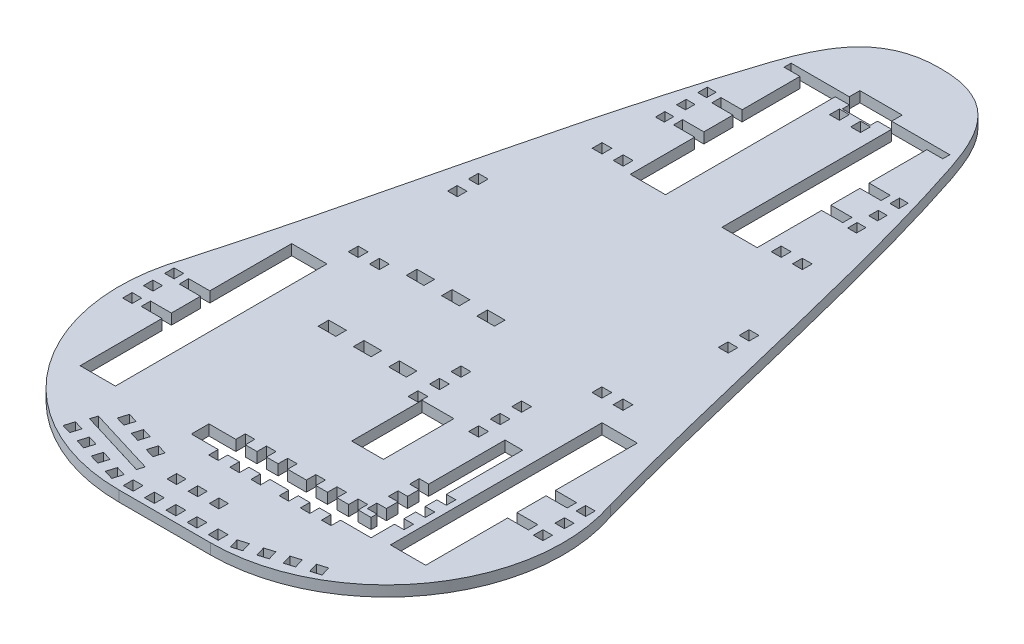
SolidWorks part; units mm, degrees
ref_plane "Front Plane" through (0, 0, 0) normal (0, 0, 1) x (1, 0, 0)
ref_plane "Top Plane" through (0, 0, 0) normal (0, 1, 0) x (1, 0, 0)
ref_plane "Right Plane" through (0, 0, 0) normal (1, 0, 0) x (0, 0, -1)
sketch "Sketch1" plane through (0, 0, 0) normal (0, 1, 0) x (1, 0, 0)
  line L0 (54.872, 210.7624) -> (54.872, -9.2376) construction
  line L1 (41.9035, -9.2376) -> (67.8405, -9.2376)
  line L6 (5.872, 75.7624) -> (15.872, 75.7624)
  line L7 (54.872, -9.2376) -> (64.872, -9.2376)
  line L8 (54.872, -9.2376) -> (44.872, -9.2376)
  line L9 (5.872, 75.7624) -> (5.872, 15.7624)
  line L10 (5.872, 15.7624) -> (15.872, 15.7624)
  line L11 (15.872, 75.7624) -> (15.872, 15.7624)
  line L12 (5.872, 75.7624) -> (15.872, 15.7624) construction
  line L13 (5.872, 15.7624) -> (15.872, 75.7624) construction
  line L18 (-0.128, 52.5374) -> (5.872, 52.5374)
  line L19 (-0.128, 52.5374) -> (-0.128, 49.8874)
  line L35 (103.872, 15.7624) -> (93.872, 15.7624)
  line L36 (93.872, 75.7624) -> (93.872, 15.7624)
  line L37 (103.872, 75.7624) -> (93.872, 75.7624)
  line L38 (103.872, 75.7624) -> (103.872, 15.7624)
  line L40 (36.872, 190.7624) -> (46.872, 190.7624)
  line L41 (36.872, 190.7624) -> (36.872, 140.7624)
  line L42 (36.872, 140.7624) -> (46.872, 140.7624)
  line L43 (46.872, 190.7624) -> (46.872, 140.7624)
  line L44 (36.872, 190.7624) -> (46.872, 140.7624) construction
  line L45 (36.872, 140.7624) -> (46.872, 190.7624) construction
  line L46 (10.872, 45.7624) -> (-10.2667, 45.7624) construction
  line L63 (72.872, 140.7624) -> (62.872, 140.7624)
  line L64 (62.872, 190.7624) -> (62.872, 140.7624)
  line L65 (72.872, 190.7624) -> (62.872, 190.7624)
  line L66 (72.872, 190.7624) -> (72.872, 140.7624)
  line L78 (114.572, 47.1124) -> (111.872, 44.4124) construction
  line L79 (114.572, 44.4124) -> (111.872, 47.1124) construction
  line L80 (114.572, 50.4124) -> (111.872, 53.1124) construction
  line L81 (114.572, 53.1124) -> (111.872, 50.4124) construction
  line L82 (109.7728, 38.9874) -> (103.7728, 41.6374) construction
  line L83 (109.7728, 41.6374) -> (103.7728, 38.9874) construction
  line L84 (109.872, 49.8874) -> (103.872, 52.5374) construction
  line L85 (109.872, 52.5374) -> (103.872, 49.8874) construction
  line L86 (111.7728, 41.1124) -> (111.7728, 38.4124)
  line L87 (114.4728, 38.4124) -> (111.7728, 38.4124)
  line L88 (114.4728, 41.1124) -> (114.4728, 38.4124)
  line L89 (111.872, 44.4124) -> (111.872, 47.1124)
  line L90 (114.572, 47.1124) -> (111.872, 47.1124)
  line L91 (114.572, 44.4124) -> (114.572, 47.1124)
  line L92 (41.872, 165.7624) -> (24.9145, 165.7624) construction
  line L93 (30.872, 172.4874) -> (36.872, 172.4874)
  line L94 (30.872, 172.4874) -> (30.872, 169.8874)
  line L95 (30.872, 169.8874) -> (36.872, 169.8874)
  line L96 (36.872, 172.4874) -> (36.872, 169.8874)
  line L97 (30.872, 172.4874) -> (36.872, 169.8874) construction
  line L98 (30.872, 169.8874) -> (36.872, 172.4874) construction
  line L103 (26.372, 161.1124) -> (28.872, 161.1124)
  line L104 (26.372, 173.1124) -> (28.872, 173.1124)
  line L105 (30.872, 161.6374) -> (36.872, 161.6374)
  line L106 (30.872, 161.6374) -> (30.872, 159.0374)
  line L107 (30.872, 159.0374) -> (36.872, 159.0374)
  line L108 (36.872, 161.6374) -> (36.872, 159.0374)
  line L109 (30.872, 161.6374) -> (36.872, 159.0374) construction
  line L110 (30.872, 159.0374) -> (36.872, 161.6374) construction
  line L111 (26.372, 173.1124) -> (26.372, 170.4124)
  line L112 (26.372, 170.4124) -> (28.872, 170.4124)
  line L113 (28.872, 173.1124) -> (28.872, 170.4124)
  line L114 (26.372, 173.1124) -> (28.872, 170.4124) construction
  line L115 (26.372, 170.4124) -> (28.872, 173.1124) construction
  line L116 (26.372, 164.4124) -> (28.872, 164.4124)
  line L117 (26.372, 164.4124) -> (26.372, 167.1124)
  line L118 (26.372, 167.1124) -> (28.872, 167.1124)
  line L119 (28.872, 164.4124) -> (28.872, 167.1124)
  line L120 (26.372, 164.4124) -> (28.872, 167.1124) construction
  line L121 (26.372, 167.1124) -> (28.872, 164.4124) construction
  line L122 (26.372, 161.1124) -> (26.372, 158.4124)
  line L123 (26.372, 158.4124) -> (28.872, 158.4124)
  line L124 (28.872, 161.1124) -> (28.872, 158.4124)
  line L125 (83.372, 167.1124) -> (80.872, 164.4124) construction
  line L126 (83.372, 164.4124) -> (80.872, 167.1124) construction
  line L127 (83.372, 170.4124) -> (80.872, 173.1124) construction
  line L128 (83.372, 173.1124) -> (80.872, 170.4124) construction
  line L129 (78.872, 159.0374) -> (72.872, 161.6374) construction
  line L130 (78.872, 161.6374) -> (72.872, 159.0374) construction
  line L131 (78.872, 169.8874) -> (72.872, 172.4874) construction
  line L132 (78.872, 172.4874) -> (72.872, 169.8874) construction
  line L133 (80.872, 161.1124) -> (80.872, 158.4124)
  line L134 (83.372, 158.4124) -> (80.872, 158.4124)
  line L135 (83.372, 161.1124) -> (83.372, 158.4124)
  line L136 (80.872, 164.4124) -> (80.872, 167.1124)
  line L137 (83.372, 167.1124) -> (80.872, 167.1124)
  line L138 (83.372, 164.4124) -> (83.372, 167.1124)
  line L139 (83.372, 164.4124) -> (80.872, 164.4124)
  line L140 (80.872, 173.1124) -> (80.872, 170.4124)
  line L141 (83.372, 170.4124) -> (80.872, 170.4124)
  line L142 (83.372, 173.1124) -> (83.372, 170.4124)
  line L143 (72.872, 161.6374) -> (72.872, 159.0374)
  line L144 (78.872, 159.0374) -> (72.872, 159.0374)
  line L145 (78.872, 161.6374) -> (78.872, 159.0374)
  line L146 (78.872, 161.6374) -> (72.872, 161.6374)
  line L147 (83.372, 173.1124) -> (80.872, 173.1124)
  line L148 (83.372, 161.1124) -> (80.872, 161.1124)
  line L149 (72.872, 172.4874) -> (72.872, 169.8874)
  line L150 (78.872, 169.8874) -> (72.872, 169.8874)
  line L151 (78.872, 172.4874) -> (78.872, 169.8874)
  line L152 (78.872, 172.4874) -> (72.872, 172.4874)
  line L153 (-0.128, 49.8874) -> (5.872, 49.8874)
  line L154 (5.872, 52.5374) -> (5.872, 49.8874)
  line L155 (-0.128, 52.5374) -> (5.872, 49.8874) construction
  line L156 (-0.128, 49.8874) -> (5.872, 52.5374) construction
  line L157 (-4.7289, 41.1124) -> (-2.0289, 41.1124)
  line L158 (-4.828, 53.1124) -> (-2.128, 53.1124)
  line L159 (-0.0289, 41.6374) -> (5.9711, 41.6374)
  line L160 (-0.0289, 41.6374) -> (-0.0289, 38.9874)
  line L161 (-0.0289, 38.9874) -> (5.9711, 38.9874)
  line L162 (5.9711, 41.6374) -> (5.9711, 38.9874)
  line L163 (-0.0289, 41.6374) -> (5.9711, 38.9874) construction
  line L164 (-0.0289, 38.9874) -> (5.9711, 41.6374) construction
  line L165 (-4.828, 53.1124) -> (-4.828, 50.4124)
  line L166 (-4.828, 50.4124) -> (-2.128, 50.4124)
  line L167 (-2.128, 53.1124) -> (-2.128, 50.4124)
  line L168 (-4.828, 53.1124) -> (-2.128, 50.4124) construction
  line L169 (-4.828, 50.4124) -> (-2.128, 53.1124) construction
  line L170 (-4.828, 44.4124) -> (-2.128, 44.4124)
  line L171 (-4.828, 44.4124) -> (-4.828, 47.1124)
  line L172 (-4.828, 47.1124) -> (-2.128, 47.1124)
  line L173 (-2.128, 44.4124) -> (-2.128, 47.1124)
  line L174 (-4.828, 44.4124) -> (-2.128, 47.1124) construction
  line L175 (-4.828, 47.1124) -> (-2.128, 44.4124) construction
  line L176 (-4.7289, 41.1124) -> (-4.7289, 38.4124)
  line L177 (-4.7289, 38.4124) -> (-2.0289, 38.4124)
  line L178 (-2.0289, 41.1124) -> (-2.0289, 38.4124)
  line L179 (114.572, 44.4124) -> (111.872, 44.4124)
  line L180 (111.872, 53.1124) -> (111.872, 50.4124)
  line L181 (114.572, 50.4124) -> (111.872, 50.4124)
  line L182 (114.572, 53.1124) -> (114.572, 50.4124)
  line L183 (103.7728, 41.6374) -> (103.7728, 38.9874)
  line L184 (109.7728, 38.9874) -> (103.7728, 38.9874)
  line L185 (109.7728, 41.6374) -> (109.7728, 38.9874)
  line L186 (109.7728, 41.6374) -> (103.7728, 41.6374)
  line L187 (114.572, 53.1124) -> (111.872, 53.1124)
  line L188 (114.4728, 41.1124) -> (111.7728, 41.1124)
  line L189 (103.872, 52.5374) -> (103.872, 49.8874)
  line L190 (109.872, 49.8874) -> (103.872, 49.8874)
  line L191 (109.872, 52.5374) -> (109.872, 49.8874)
  line L192 (109.872, 52.5374) -> (103.872, 52.5374)
  line L193 (103.872, 45.7624) -> (5.872, 45.7624) construction
  line L200 (62.872, 55.7624) -> (71.872, 55.7624)
  line L201 (62.872, 55.7624) -> (62.872, 35.7624)
  line L202 (62.872, 35.7624) -> (71.872, 35.7624)
  line L203 (71.872, 55.7624) -> (71.872, 35.7624)
  line L204 (62.872, 55.7624) -> (71.872, 35.7624) construction
  line L205 (62.872, 35.7624) -> (71.872, 55.7624) construction
  line L211 (39.9211, 62.2172) -> (44.9211, 62.2172)
  line L213 (59.9211, 69.7172) -> (62.7211, 69.7172)
  line L214 (59.9211, 57.5172) -> (62.7211, 57.5172)
  line L215 (59.9211, 57.5172) -> (59.9211, 54.7172)
  line L216 (59.9211, 54.7172) -> (62.7211, 54.7172)
  line L217 (62.7211, 57.5172) -> (62.7211, 54.7172)
  line L218 (59.9211, 57.5172) -> (62.7211, 54.7172) construction
  line L219 (59.9211, 54.7172) -> (62.7211, 57.5172) construction
  line L220 (59.9211, 69.7172) -> (59.9211, 66.9172)
  line L221 (59.9211, 66.9172) -> (62.7211, 66.9172)
  line L222 (62.7211, 69.7172) -> (62.7211, 66.9172)
  line L223 (59.9211, 63.6172) -> (62.7211, 63.6172)
  line L224 (59.9211, 63.6172) -> (59.9211, 60.8172)
  line L225 (59.9211, 60.8172) -> (62.7211, 60.8172)
  line L226 (62.7211, 63.6172) -> (62.7211, 60.8172)
  line L227 (77.1211, 69.7172) -> (79.9211, 69.7172)
  line L228 (77.1211, 57.5172) -> (79.9211, 57.5172)
  line L229 (77.1211, 57.5172) -> (77.1211, 54.7172)
  line L230 (77.1211, 54.7172) -> (79.9211, 54.7172)
  line L231 (79.9211, 57.5172) -> (79.9211, 54.7172)
  line L232 (77.1211, 69.7172) -> (77.1211, 66.9172)
  line L233 (77.1211, 66.9172) -> (79.9211, 66.9172)
  line L234 (79.9211, 69.7172) -> (79.9211, 66.9172)
  line L235 (77.1211, 63.6172) -> (79.9211, 63.6172)
  line L236 (77.1211, 63.6172) -> (77.1211, 60.8172)
  line L237 (77.1211, 60.8172) -> (79.9211, 60.8172)
  line L238 (79.9211, 63.6172) -> (79.9211, 60.8172)
  line L244 (49.9211, 62.2172) -> (54.9211, 62.2172)
  line L245 (49.9211, 62.2172) -> (49.9211, 59.2172)
  line L246 (49.9211, 59.2172) -> (54.9211, 59.2172)
  line L247 (54.9211, 62.2172) -> (54.9211, 59.2172)
  line L248 (49.9211, 61.7172) -> (54.9211, 58.7172) construction
  line L249 (49.9211, 58.7172) -> (54.9211, 61.7172) construction
  line L250 (39.9211, 62.2172) -> (39.9211, 59.2172)
  line L251 (39.9211, 59.2172) -> (44.9211, 59.2172)
  line L252 (44.9211, 62.2172) -> (44.9211, 59.2172)
  line L253 (29.9211, 62.2172) -> (34.9211, 62.2172)
  line L254 (29.9211, 62.2172) -> (29.9211, 59.2172)
  line L255 (29.9211, 59.2172) -> (34.9211, 59.2172)
  line L256 (34.9211, 62.2172) -> (34.9211, 59.2172)
  line L257 (49.9211, 87.2172) -> (54.9211, 87.2172)
  line L258 (49.9211, 87.2172) -> (49.9211, 84.2172)
  line L259 (49.9211, 84.2172) -> (54.9211, 84.2172)
  line L260 (54.9211, 87.2172) -> (54.9211, 84.2172)
  line L261 (39.9211, 87.2172) -> (44.9211, 87.2172)
  line L262 (39.9211, 87.2172) -> (39.9211, 84.2172)
  line L263 (39.9211, 84.2172) -> (44.9211, 84.2172)
  line L264 (44.9211, 87.2172) -> (44.9211, 84.2172)
  line L265 (29.9211, 87.2172) -> (34.9211, 87.2172)
  line L266 (29.9211, 87.2172) -> (29.9211, 84.2172)
  line L267 (29.9211, 84.2172) -> (34.9211, 84.2172)
  line L268 (34.9211, 87.2172) -> (34.9211, 84.2172)
  line L279 (15.072, 113.4624) -> (17.872, 113.4624)
  line L284 (15.0729, 119.4624) -> (17.8729, 119.4624)
  line L285 (15.0729, 119.4624) -> (15.0729, 116.6624)
  line L286 (15.0729, 116.6624) -> (17.8729, 116.6624)
  line L287 (17.8729, 119.4624) -> (17.8729, 116.6624)
  line L288 (15.072, 113.4624) -> (15.072, 110.7624)
  line L289 (15.072, 110.7624) -> (17.872, 110.7624)
  line L290 (17.872, 113.4624) -> (17.872, 110.7624)
  line L332 (15.9201, 84.5624) -> (18.7201, 84.5624)
  line L333 (15.9201, 84.5624) -> (15.9201, 81.7624)
  line L334 (15.9201, 81.7624) -> (18.7201, 81.7624)
  line L335 (18.7201, 84.5624) -> (18.7201, 81.7624)
  line L339 (21.9201, 84.5624) -> (24.7201, 84.5624)
  line L340 (21.9201, 84.5624) -> (21.9201, 81.7624)
  line L341 (21.9201, 81.7624) -> (24.7201, 81.7624)
  line L342 (24.7201, 84.5624) -> (24.7201, 81.7624)
  line L363 (25.072, 144.5629) -> (27.872, 144.5629)
  line L368 (25.072, 144.5629) -> (25.072, 141.7629)
  line L369 (25.072, 141.7629) -> (27.872, 141.7629)
  line L370 (27.872, 144.5629) -> (27.872, 141.7629)
  line L371 (31.072, 144.5624) -> (33.872, 144.5624)
  line L372 (31.072, 144.5624) -> (31.072, 141.7624)
  line L373 (31.072, 141.7624) -> (33.872, 141.7624)
  line L374 (33.872, 144.5624) -> (33.872, 141.7624)
  line L375 (75.872, 144.5624) -> (75.872, 141.7624)
  line L376 (78.672, 141.7624) -> (75.872, 141.7624)
  line L377 (78.672, 144.5624) -> (78.672, 141.7624)
  line L378 (78.672, 144.5624) -> (75.872, 144.5624)
  line L379 (81.872, 144.5629) -> (81.872, 141.7629)
  line L380 (84.672, 141.7629) -> (81.872, 141.7629)
  line L381 (84.672, 144.5629) -> (84.672, 141.7629)
  line L382 (84.672, 144.5629) -> (81.872, 144.5629)
  line L383 (50.4739, 186.4794) -> (50.472, 183.6794)
  line L384 (32.372, 190.884) -> (77.372, 190.884)
  line L385 (32.372, 190.884) -> (32.372, 188.884)
  line L386 (32.372, 188.884) -> (77.372, 188.884)
  line L387 (77.372, 190.884) -> (77.372, 188.884)
  line L388 (48.872, 193.884) -> (60.872, 193.884)
  line L389 (48.872, 193.884) -> (48.872, 190.884)
  line L390 (48.872, 190.884) -> (60.872, 190.884)
  line L391 (60.872, 193.884) -> (60.872, 190.884)
  line L392 (53.272, 183.6794) -> (50.472, 183.6794)
  line L393 (53.272, 186.4794) -> (53.272, 183.6794)
  line L394 (53.272, 186.4794) -> (50.4739, 186.4794)
  line L404 (85.372, 55.7624) -> (88.372, 55.7624)
  line L405 (85.372, 55.7624) -> (85.372, 15.7624)
  line L406 (85.372, 15.7624) -> (88.372, 15.7624)
  line L407 (88.372, 55.7624) -> (88.372, 15.7624)
  line L408 (44.372, 18.7624) -> (88.372, 18.7624)
  line L409 (44.372, 18.7624) -> (44.372, 15.7624)
  line L410 (44.372, 15.7624) -> (88.372, 15.7624)
  line L411 (88.372, 18.7624) -> (88.372, 15.7624)
  line L471 (41.9035, -9.2376) -> (64.872, -9.2376)
  line L480 (46.022, 22.4624) -> (46.022, 19.7624)
  line L481 (48.722, 19.7624) -> (46.022, 19.7624)
  line L482 (48.722, 22.4624) -> (48.722, 19.7624)
  line L483 (48.722, 22.4624) -> (46.022, 22.4624)
  line L484 (52.022, 22.4624) -> (52.022, 19.7624)
  line L485 (54.722, 19.7624) -> (52.022, 19.7624)
  line L486 (54.722, 22.4624) -> (54.722, 19.7624)
  line L487 (54.722, 22.4624) -> (52.022, 22.4624)
  line L488 (58.022, 22.4624) -> (58.022, 19.7624)
  line L489 (60.722, 19.7624) -> (58.022, 19.7624)
  line L490 (60.722, 22.4624) -> (60.722, 19.7624)
  line L491 (60.722, 22.4624) -> (58.022, 22.4624)
  line L492 (56.472, 186.4794) -> (59.2701, 186.4794)
  line L493 (56.472, 186.4794) -> (56.472, 183.6794)
  line L494 (56.472, 183.6794) -> (59.272, 183.6794)
  line L495 (59.2701, 186.4794) -> (59.272, 183.6794)
  line L496 (94.672, 113.4624) -> (94.672, 110.7624)
  line L497 (94.672, 110.7624) -> (91.872, 110.7624)
  line L498 (91.872, 113.4624) -> (91.872, 110.7624)
  line L499 (94.672, 113.4624) -> (91.872, 113.4624)
  line L500 (94.671, 119.4624) -> (94.671, 116.6624)
  line L501 (94.671, 116.6624) -> (91.871, 116.6624)
  line L502 (91.871, 119.4624) -> (91.871, 116.6624)
  line L503 (94.671, 119.4624) -> (91.871, 119.4624)
  line L512 (87.8238, 84.5624) -> (87.8238, 81.7624)
  line L513 (87.8238, 81.7624) -> (85.0238, 81.7624)
  line L514 (85.0238, 84.5624) -> (85.0238, 81.7624)
  line L515 (87.8238, 84.5624) -> (85.0238, 84.5624)
  line L516 (93.8238, 84.5624) -> (93.8238, 81.7624)
  line L517 (93.8238, 81.7624) -> (91.0238, 81.7624)
  line L518 (91.0238, 84.5624) -> (91.0238, 81.7624)
  line L519 (93.8238, 84.5624) -> (91.0238, 84.5624)
  line L520 (76.372, 18.7624) -> (76.372, 15.7624) construction
  line L521 (64.372, 18.7624) -> (88.372, 18.7624)
  line L522 (64.372, 18.7624) -> (64.372, 15.7624)
  line L523 (64.372, 15.7624) -> (88.372, 15.7624)
  line L524 (88.372, 18.7624) -> (88.372, 15.7624)
  line L525 (76.372, 27.5136) -> (76.372, 8.1564) construction
  line L526 (85.372, 25.7624) -> (88.372, 25.7624) construction
  line L527 (85.372, 35.7624) -> (88.372, 35.7624)
  line L528 (85.372, 35.7624) -> (85.372, 15.7624)
  line L529 (85.372, 15.7624) -> (88.372, 15.7624)
  line L530 (88.372, 35.7624) -> (88.372, 15.7624)
  line L531 (91.4767, 25.7624) -> (69.6189, 25.7624) construction
  line L532 (44.372, 17.2624) -> (64.372, 17.2624) construction
  line L537 (84.372, 57.7624) -> (89.372, 57.7624)
  line L538 (84.372, 57.7624) -> (84.372, 14.7624)
  line L539 (84.372, 14.7624) -> (89.372, 14.7624)
  line L540 (89.372, 57.7624) -> (89.372, 14.7624)
  line L541 (42.372, 19.7624) -> (89.372, 19.7624)
  line L542 (42.372, 19.7624) -> (42.372, 14.7624)
  line L543 (42.372, 14.7624) -> (89.372, 14.7624)
  line L544 (89.372, 19.7624) -> (89.372, 14.7624)
  line L545 (74.722, 14.7624) -> (74.722, 12.0624)
  line L546 (74.722, 12.0624) -> (72.022, 12.0624)
  line L547 (72.022, 14.7624) -> (72.022, 12.0624)
  line L548 (74.722, 14.7624) -> (72.022, 14.7624)
  line L553 (80.722, 14.7624) -> (80.722, 12.0624)
  line L554 (78.022, 14.7624) -> (80.722, 14.7624)
  line L555 (78.022, 14.7624) -> (78.022, 12.0624)
  line L556 (78.022, 12.0624) -> (80.722, 12.0624)
  line L557 (64.372, 17.2624) -> (88.372, 17.2624) construction
  line L558 (78.022, 19.7624) -> (80.722, 19.7624)
  line L559 (78.022, 19.7624) -> (78.022, 22.4624)
  line L560 (78.022, 22.4624) -> (80.722, 22.4624)
  line L561 (80.722, 19.7624) -> (80.722, 22.4624)
  line L562 (72.022, 19.7624) -> (72.022, 22.4624)
  line L563 (74.722, 19.7624) -> (72.022, 19.7624)
  line L564 (74.722, 19.7624) -> (74.722, 22.4624)
  line L565 (74.722, 22.4624) -> (72.022, 22.4624)
  line L566 (81.672, 27.4124) -> (84.372, 27.4124)
  line L567 (81.672, 27.4124) -> (81.672, 30.1124)
  line L568 (81.672, 30.1124) -> (84.372, 30.1124)
  line L569 (84.372, 27.4124) -> (84.372, 30.1124)
  line L574 (86.872, 35.7624) -> (86.872, 15.7624) construction
  line L575 (81.672, 24.1124) -> (81.672, 21.4124)
  line L576 (81.672, 21.4124) -> (84.372, 21.4124)
  line L577 (84.372, 24.1124) -> (84.372, 21.4124)
  line L578 (81.672, 24.1124) -> (84.372, 24.1124)
  line L579 (92.072, 24.1124) -> (89.372, 24.1124)
  line L580 (89.372, 24.1124) -> (89.372, 21.4124)
  line L581 (92.072, 21.4124) -> (89.372, 21.4124)
  line L582 (92.072, 24.1124) -> (92.072, 21.4124)
  line L583 (92.072, 27.4124) -> (92.072, 30.1124)
  line L584 (92.072, 30.1124) -> (89.372, 30.1124)
  line L585 (89.372, 27.4124) -> (89.372, 30.1124)
  line L586 (92.072, 27.4124) -> (89.372, 27.4124)
  line L588 (50.872, 188.884) -> (58.872, 188.884)
  line L589 (50.872, 188.884) -> (50.872, 186.884)
  line L590 (50.872, 186.884) -> (58.872, 186.884)
  line L591 (58.872, 188.884) -> (58.872, 186.884)
  line L659 (60.722, 0.2624) -> (58.022, 0.2624)
  line L660 (59.522, -4.7376) -> (62.322, -4.7376)
  line L661 (53.522, -4.7376) -> (56.322, -4.7376)
  line L662 (53.522, -4.7376) -> (53.522, -7.5376)
  line L663 (53.522, -7.5376) -> (56.322, -7.5376)
  line L664 (56.322, -4.7376) -> (56.322, -7.5376)
  line L665 (59.522, -4.7376) -> (59.522, -7.5376)
  line L666 (59.522, -7.5376) -> (62.322, -7.5376)
  line L667 (62.322, -4.7376) -> (62.322, -7.5376)
  line L668 (65.522, -4.7376) -> (68.322, -4.7376)
  line L669 (65.522, -4.7376) -> (65.522, -7.5376)
  line L670 (65.522, -7.5376) -> (68.322, -7.5376)
  line L671 (68.322, -4.7376) -> (68.322, -7.5376)
  line L672 (44.222, -4.7376) -> (44.222, -7.5376)
  line L673 (44.222, -7.5376) -> (41.422, -7.5376)
  line L674 (41.422, -4.7376) -> (41.422, -7.5376)
  line L675 (44.222, -4.7376) -> (41.422, -4.7376)
  line L676 (50.222, -4.7376) -> (50.222, -7.5376)
  line L677 (50.222, -7.5376) -> (47.422, -7.5376)
  line L678 (47.422, -4.7376) -> (47.422, -7.5376)
  line L679 (50.222, -4.7376) -> (47.422, -4.7376)
  line L708 (60.722, 12.0624) -> (58.022, 12.0624)
  line L709 (60.722, 12.0624) -> (60.722, 14.7624)
  line L710 (60.722, 14.7624) -> (58.022, 14.7624)
  line L711 (58.022, 12.0624) -> (58.022, 14.7624)
  line L712 (54.722, 12.0624) -> (52.022, 12.0624)
  line L713 (54.722, 12.0624) -> (54.722, 14.7624)
  line L714 (54.722, 14.7624) -> (52.022, 14.7624)
  line L715 (52.022, 12.0624) -> (52.022, 14.7624)
  line L716 (48.722, 12.0624) -> (46.022, 12.0624)
  line L717 (48.722, 12.0624) -> (48.722, 14.7624)
  line L718 (48.722, 14.7624) -> (46.022, 14.7624)
  line L719 (46.022, 12.0624) -> (46.022, 14.7624)
  line L720 (15.872, 15.7624) -> (15.872, -1.9267) construction
  line L721 (93.872, 15.7624) -> (93.872, -1.9267) construction
  line L722 (60.722, 0.2624) -> (60.722, 2.9624)
  line L755 (68.722, 14.7624) -> (68.722, 12.0624)
  line L756 (66.022, 14.7624) -> (68.722, 14.7624)
  line L757 (66.022, 14.7624) -> (66.022, 12.0624)
  line L758 (66.022, 12.0624) -> (68.722, 12.0624)
  line L759 (66.022, 19.7624) -> (68.722, 19.7624)
  line L760 (66.022, 19.7624) -> (66.022, 22.4624)
  line L761 (66.022, 22.4624) -> (68.722, 22.4624)
  line L762 (68.722, 19.7624) -> (68.722, 22.4624)
  line L763 (81.672, 33.4124) -> (84.372, 33.4124)
  line L764 (81.672, 33.4124) -> (81.672, 36.1124)
  line L765 (81.672, 36.1124) -> (84.372, 36.1124)
  line L766 (84.372, 33.4124) -> (84.372, 36.1124)
  line L767 (92.072, 33.4124) -> (92.072, 36.1124)
  line L768 (92.072, 36.1124) -> (89.372, 36.1124)
  line L769 (89.372, 33.4124) -> (89.372, 36.1124)
  line L770 (92.072, 33.4124) -> (89.372, 33.4124)
  line L771 (24.7054, -0.4214) -> (27.383, -1.2401)
  line L788 (18.9675, 1.3328) -> (21.6452, 0.5142)
  line L805 (60.722, 2.9624) -> (58.022, 2.9624)
  line L806 (42.372, 19.7624) -> (38.4108, 19.7624)
  line L807 (42.372, 19.7624) -> (42.372, 14.7624)
  line L808 (42.372, 14.7624) -> (38.4108, 14.7624)
  line L809 (38.4108, 19.7624) -> (38.4108, 14.7624)
  line L810 (58.022, 0.2624) -> (58.022, 2.9624)
  line L811 (54.722, 0.2624) -> (52.022, 0.2624)
  line L812 (54.722, 0.2624) -> (54.722, 2.9624)
  line L813 (54.722, 2.9624) -> (52.022, 2.9624)
  line L814 (52.022, 0.2624) -> (52.022, 2.9624)
  line L815 (48.722, 0.2624) -> (46.022, 0.2624)
  line L816 (48.722, 0.2624) -> (48.722, 2.9624)
  line L817 (48.722, 2.9624) -> (46.022, 2.9624)
  line L818 (46.022, 0.2624) -> (46.022, 2.9624)
  line L823 (43.637, -40.6137) -> (46.437, -40.6137)
  line L824 (37.637, -40.6137) -> (40.437, -40.6137)
  line L825 (37.637, -40.6137) -> (37.637, -43.4137)
  line L826 (37.637, -43.4137) -> (40.437, -43.4137)
  line L827 (40.437, -40.6137) -> (40.437, -43.4137)
  line L828 (43.637, -40.6137) -> (43.637, -43.4137)
  line L829 (43.637, -43.4137) -> (46.437, -43.4137)
  line L830 (46.437, -40.6137) -> (46.437, -43.4137)
  line L831 (48.037, -35.6137) -> (48.037, -37.6137) construction
  line L832 (38.037, -35.6137) -> (58.037, -35.6137)
  line L833 (38.037, -35.6137) -> (38.037, -37.6137)
  line L834 (38.037, -37.6137) -> (58.037, -37.6137)
  line L835 (58.037, -35.6137) -> (58.037, -37.6137)
  line L836 (52.437, -40.6137) -> (52.437, -43.4137)
  line L837 (52.437, -43.4137) -> (49.637, -43.4137)
  line L838 (49.637, -40.6137) -> (49.637, -43.4137)
  line L839 (52.437, -40.6137) -> (49.637, -40.6137)
  line L840 (58.437, -43.4137) -> (55.637, -43.4137)
  line L841 (55.637, -40.6137) -> (55.637, -43.4137)
  line L842 (58.437, -40.6137) -> (55.637, -40.6137)
  line L843 (58.437, -40.6137) -> (58.437, -43.4137)
  line L844 (46.437, -29.8137) -> (49.237, -29.8137)
  line L845 (46.437, -29.8137) -> (46.437, -32.6137)
  line L846 (46.437, -32.6137) -> (49.237, -32.6137)
  line L847 (49.237, -29.8137) -> (49.237, -32.6137)
  line L848 (40.437, -29.8137) -> (43.237, -29.8137)
  line L849 (40.437, -29.8137) -> (40.437, -32.6137)
  line L850 (40.437, -32.6137) -> (43.237, -32.6137)
  line L851 (43.237, -29.8137) -> (43.237, -32.6137)
  line L852 (55.637, -29.8137) -> (55.637, -32.6137)
  line L853 (55.637, -32.6137) -> (52.837, -32.6137)
  line L854 (52.837, -29.8137) -> (52.837, -32.6137)
  line L855 (55.637, -29.8137) -> (52.837, -29.8137)
  line L856 (18.9675, 1.3328) -> (18.1489, -1.3448)
  line L857 (18.1489, -1.3448) -> (20.8266, -2.1635)
  line L858 (21.6452, 0.5142) -> (20.8266, -2.1635)
  line L859 (24.7054, -0.4214) -> (23.8867, -3.0991)
  line L860 (23.8867, -3.0991) -> (26.5644, -3.9177)
  line L861 (27.383, -1.2401) -> (26.5644, -3.9177)
  line L862 (30.375, 3.0737) -> (29.7902, 1.1611) construction
  line L863 (20.8119, 5.9974) -> (39.938, 0.15)
  line L864 (20.8119, 5.9974) -> (20.2272, 4.0848)
  line L865 (20.2272, 4.0848) -> (39.3533, -1.7626)
  line L866 (39.938, 0.15) -> (39.3533, -1.7626)
  line L867 (33.1209, -2.9943) -> (32.3022, -5.6719)
  line L868 (32.3022, -5.6719) -> (29.6246, -4.8533)
  line L869 (30.4432, -2.1756) -> (29.6246, -4.8533)
  line L870 (33.1209, -2.9943) -> (30.4432, -2.1756)
  line L871 (38.04, -7.4262) -> (35.3624, -6.6075)
  line L872 (36.181, -3.9299) -> (35.3624, -6.6075)
  line L873 (38.8587, -4.7485) -> (36.181, -3.9299)
  line L874 (38.8587, -4.7485) -> (38.04, -7.4262)
  line L875 (30.5406, 9.088) -> (33.2183, 8.2694)
  line L876 (30.5406, 9.088) -> (29.722, 6.4104)
  line L877 (29.722, 6.4104) -> (32.3997, 5.5917)
  line L878 (33.2183, 8.2694) -> (32.3997, 5.5917)
  line L879 (24.8028, 10.8423) -> (27.4805, 10.0236)
  line L880 (24.8028, 10.8423) -> (23.9842, 8.1646)
  line L881 (23.9842, 8.1646) -> (26.6618, 7.346)
  line L882 (27.4805, 10.0236) -> (26.6618, 7.346)
  line L883 (39.3386, 6.3982) -> (38.52, 3.7206)
  line L884 (38.52, 3.7206) -> (35.8423, 4.5392)
  line L885 (36.661, 7.2169) -> (35.8423, 4.5392)
  line L886 (39.3386, 6.3982) -> (36.661, 7.2169)
  line L887 (70.8852, -4.7485) -> (71.7039, -7.4262)
  line L888 (70.8852, -4.7485) -> (73.5629, -3.9299)
  line L889 (73.5629, -3.9299) -> (74.3815, -6.6075)
  line L890 (71.7039, -7.4262) -> (74.3815, -6.6075)
  line L891 (76.6231, -2.9943) -> (79.3007, -2.1756)
  line L892 (79.3007, -2.1756) -> (80.1194, -4.8533)
  line L893 (77.4417, -5.6719) -> (80.1194, -4.8533)
  line L894 (76.6231, -2.9943) -> (77.4417, -5.6719)
  line L895 (85.0386, -0.4214) -> (85.8572, -3.0991)
  line L896 (85.8572, -3.0991) -> (83.1795, -3.9177)
  line L897 (82.3609, -1.2401) -> (83.1795, -3.9177)
  line L898 (85.0386, -0.4214) -> (82.3609, -1.2401)
  line L899 (90.7764, 1.3328) -> (91.595, -1.3448)
  line L900 (91.595, -1.3448) -> (88.9174, -2.1635)
  line L901 (88.0987, 0.5142) -> (88.9174, -2.1635)
  line L902 (90.7764, 1.3328) -> (88.0987, 0.5142)
  arc A0 (41.9035, -9.2376) -> (-5.452, 56.8081) centre (41.9035, 40.7624) cw
  arc A1 (67.8405, -9.2376) -> (115.1959, 56.8081) centre (67.8405, 40.7624) ccw
  spline S0 degree 3 poles (54.872, 210.7624) (53.982, 210.7624) (36.6831, 210.353) (26.6517, 181.7608) (12.4717, 130.3178) (2.6705, 85.557) (-5.452, 56.8081) knots 0 0 0 0 0.011072 0.22144 0.460221 1 1 1 1
  spline S1 degree 3 poles (54.872, 210.7624) (55.7619, 210.7624) (73.0609, 210.353) (83.0922, 181.7608) (97.2722, 130.3178) (107.0734, 85.557) (115.1959, 56.8081) knots 0 0 0 0 0.011072 0.22144 0.460221 1 1 1 1
  point P4 (2.872, 51.2124)
  point P24 (10.872, 45.7624)
  point P30 (-3.478, 51.7624)
  point P33 (2.9711, 40.3124)
  point P40 (-3.478, 45.7624)
  point P50 (41.872, 165.7624)
  point P67 (33.872, 171.1874)
  point P82 (27.622, 171.7624)
  point P85 (33.872, 160.3374)
  point P92 (27.622, 165.7624)
  point P121 (82.122, 165.7624)
  point P122 (75.872, 160.3374)
  point P123 (82.122, 171.7624)
  point P124 (75.872, 171.1874)
  point P131 (113.222, 45.7624)
  point P132 (106.7728, 40.3124)
  point P133 (113.222, 51.7624)
  point P134 (106.872, 51.2124)
  point P141 (67.372, 45.7624)
  point P151 (61.3211, 56.1172)
  point P177 (52.4211, 60.2172)
  dimension "D6" = 10
  dimension "D7" = 50
  dimension "D10" = 6
  dimension "D2" = 173.1277
  dimension "D1" = 220
  dimension "D3" = 60.3239
  dimension "D4" = 10
  dimension "D5" = 10
  dimension "D8" = 60
  dimension "D9" = 6
  dimension "D11" = 25
  dimension "D12" = 2.7
  dimension "D13" = 2.7
  dimension "D14" = 2.7
  dimension "D15" = 2.7
  dimension "D16" = 2
  dimension "D17" = 2
  dimension "D18" = 39
  dimension "D19" = 2.7
  dimension "D20" = 10
  dimension "D21" = 50
  dimension "D22" = 20
  dimension "D23" = 8
  dimension "D24" = 8.25
  dimension "D25" = 0
  dimension "D26" = 0
  dimension "D27" = 3.3
  dimension "D28" = 3.3
  dimension "D29" = 8.25
  dimension "D30" = 4.125
  dimension "D31" = 2.5
  dimension "D32" = 2.7
  dimension "D33" = 2.7
  dimension "D34" = 6
  dimension "D35" = 2.6
  dimension "D36" = 8.25
  dimension "D37" = 4.125
  dimension "D38" = 2.6
  dimension "D39" = 6
  dimension "D40" = 0
  dimension "D41" = 0
  dimension "D42" = 2.5
  dimension "D43" = 2.7
  dimension "D44" = 2.5
  dimension "D45" = 2.7
  dimension "D46" = 2
  dimension "D47" = 2
  dimension "D48" = 3.3
  dimension "D49" = 2.5
  dimension "D50" = 2.7
  dimension "D51" = 3
  dimension "0.33" = 3.3
  dimension "D52" = 2
  dimension "D53" = 52
  dimension "D54" = 2
  dimension "D55" = 2.65
  dimension "D56" = 2.8
  dimension "D57" = 9
  dimension "D58" = 20
  dimension "D59" = 10
  dimension "D60" = 47
  dimension "D61" = 24
  dimension "D62" = 0
  dimension "D63" = 2.8
  dimension "D64" = 2.8
  dimension "D65" = 0
  dimension "D66" = 5
  dimension "D67" = 3
  dimension "D68" = 3
  dimension "D69" = 20
  dimension "D70" = 3.3
  dimension "D71" = 2.8
  dimension "D72" = 2.8
  dimension "D73" = 3.3
  dimension "D74" = 2.8
  dimension "D75" = 2.8
  dimension "D76" = 2.8
  dimension "D77" = 2.8
  dimension "D78" = 2.8
  dimension "D79" = 2.8
  dimension "D80" = 3.3
  dimension "D81" = 3.3
  dimension "D82" = 0
  dimension "D83" = 5
  dimension "D84" = 3
  dimension "D85" = 5
  dimension "D86" = 0
  dimension "D87" = 5
  dimension "D88" = 5
  dimension "D89" = 3
  dimension "D90" = 5
  dimension "D91" = 3
  dimension "D92" = 2.8
  dimension "D93" = 2.8
  dimension "D94" = 5
  dimension "D95" = 3
  dimension "D96" = 2.7
  dimension "D97" = 5
  dimension "D98" = 5
  dimension "D99" = 3
  dimension "D100" = 2.8
  dimension "D101" = 5
  dimension "D102" = 3.2
  dimension "D103" = 0.001
  dimension "D104" = 37
  dimension "D105" = 30
  dimension "D106" = 2.7
  dimension "D107" = 2.7
  dimension "D108" = 2.7
  dimension "D109" = 2.7
  dimension "D110" = 2.7
  dimension "D111" = 2.7
  dimension "D112" = 3.3
  dimension "D113" = 3.3
  dimension "D114" = 0
  dimension "D115" = 5
  dimension "D116" = 2.8
  dimension "D117" = 2.8
  dimension "D118" = 2
  dimension "D119" = 20
  dimension "D120" = 2.8
  dimension "D121" = 2.8
  dimension "D122" = 3.2
  dimension "D123" = 0
  dimension "D124" = 3
  dimension "D125" = 3.2
  dimension "D126" = 2.8
  dimension "D127" = 2.8
  dimension "D128" = 1.6
  dimension "D129" = 3
  dimension "D130" = 2.8
  dimension "D131" = 2.8
  dimension "D132" = 3
  dimension "D133" = 3.2
  dimension "D134" = 2.8
  dimension "D135" = 2.8
  dimension "D136" = 2
  dimension "D137" = 2.8
  dimension "0.28" = 2.8
  dimension "D139" = 2.8
  dimension "D140" = 2.8
  dimension "D141" = 2.8
  dimension "D142" = 2.8
  dimension "D143" = 3.2
  dimension "D144" = 20
  dimension "D145" = 2.7
  dimension "D146" = 2.8
  dimension "D147" = 5
  dimension "D148" = 43
  dimension "D149" = 5
  dimension "D150" = 3.2
  dimension "D151" = 1
  dimension "D152" = 2.8
  dimension "D153" = 2.8
  dimension "D154" = 3.2
  dimension "D155" = 0
  dimension "D156" = 3
  dimension "D157" = 47
  dimension "D158" = 12.5
  dimension "D159" = 4.5
  dimension "D160" = 18
  dimension "D161" = 2.5
  dimension "D162" = 3
  dimension "D163" = 45
  dimension "D164" = 2
  dimension "D165" = 22.5
  dimension "D166" = 3.2
  dimension "D167" = 12
  dimension "D168" = 3
  dimension "D169" = 0
  dimension "D170" = 6
  dimension "D171" = 2.8
  dimension "D172" = 2.8
  dimension "D173" = 0
  dimension "D174" = 0
  dimension "D175" = 0
  dimension "D176" = 1.6
  dimension "D177" = 1.7
  dimension "D178" = 2.65
  dimension "D179" = 2.7
  dimension "D180" = 2.7
  dimension "D181" = 3
  dimension "D182" = 40
  dimension "D183" = 10
  dimension "D184" = 3
  dimension "D185" = 44
  dimension "D186" = 5.5
  dimension "D187" = 0
  dimension "D188" = 0
  dimension "D189" = 2.7
  dimension "D190" = 2.7
  dimension "D191" = 1.65
  dimension "D192" = 0
  dimension "D193" = 2.8
  dimension "D194" = 2.8
  dimension "D195" = 1.6
  dimension "D196" = 3
  dimension "D197" = 2.8
  dimension "D198" = 2.8
  dimension "D199" = 3
  dimension "D200" = 3.2
  dimension "D201" = 2.7
  dimension "D202" = 0
  dimension "D203" = 2.8
  dimension "D204" = 2.7
  dimension "D205" = 0
  dimension "D206" = 3.3
  dimension "D207" = 2.7
  dimension "D208" = 2.7
  dimension "D209" = 2.7
  dimension "D210" = 2.7
  dimension "D211" = 2.7
  dimension "D212" = 2.7
  dimension "D213" = 2.7
  dimension "D214" = 2.7
  dimension "D215" = 2.7
  dimension "D217" = 2.7
  dimension "D218" = 2.7
  dimension "D219" = 2.7
  dimension "D220" = 2.7
  dimension "D221" = 2.7
  dimension "D222" = 2.7
  dimension "D223" = 1.65
  dimension "D224" = 0
  dimension "D225" = 2.7
  dimension "D226" = 8
  dimension "D227" = 4
  dimension "D228" = 2
  dimension "D229" = 0
  dimension "D230" = 2.8
  dimension "D233" = 2.8
  dimension "D234" = 2.7
  dimension "D235" = 2.8
  dimension "D236" = 3.3
  dimension "D237" = 2.7
  dimension "D238" = 2.7
  dimension "D239" = 3.3
  dimension "D240" = 2.7
  dimension "D241" = 1.35
  dimension "D242" = 3.3
  dimension "D243" = 3.2
  dimension "D244" = 2.8
  dimension "D245" = 3.2
  dimension "D246" = 0
  dimension "D247" = 2.8
  dimension "D138" = 2.8
extrude "Boss-Extrude1" add sketch "Sketch1" along normal blind 3 contours L0 S0 A0 L1 | S1 L0 L1 A1 region at (3.3293, 0, -13.1044)
